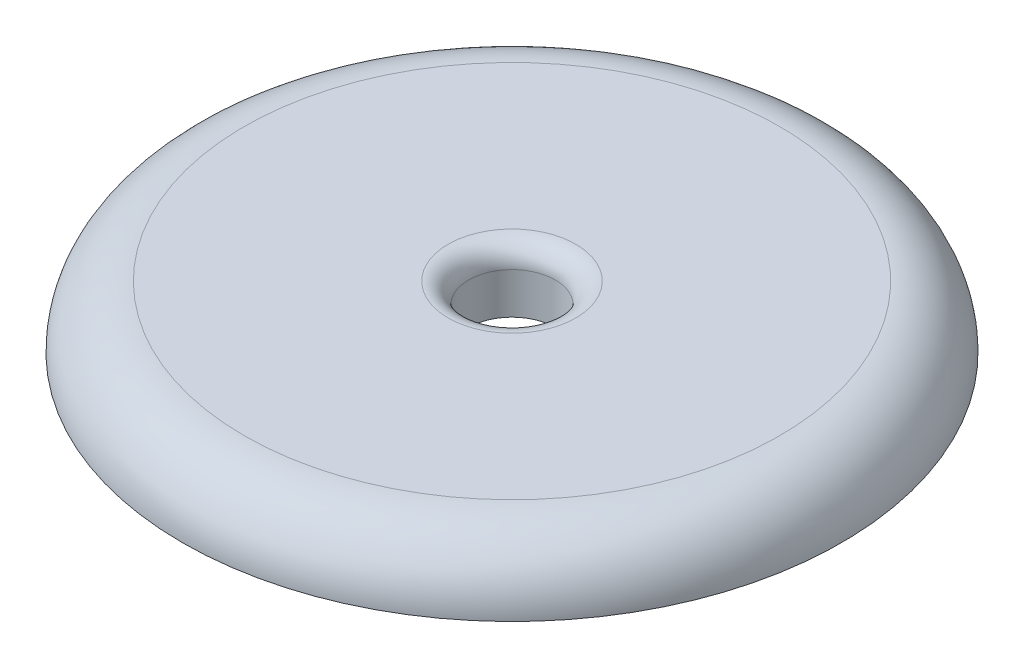
SolidWorks part; units mm, degrees
ref_plane "Спереди" through (0, 0, 0) normal (0, 0, 1) x (1, 0, 0)
ref_plane "Сверху" through (0, 0, 0) normal (0, 1, 0) x (1, 0, 0)
ref_plane "Справа" through (0, 0, 0) normal (1, 0, 0) x (0, 0, -1)
other "Configuration Table"
sketch "Эскиз1" plane through (0, 0, 0) normal (0, 1, 0) x (1, 0, 0)
  line L0 (0, 16.5661) -> (0, -15.4339) construction
  line L1 (-16, 0.5661) -> (16, 0.5661) construction
  circle A0 centre (0, 0.5661) radius 16
  circle A1 centre (0, 0.5661) radius 2.1
  dimension "D1" = 32
  dimension "D2" = 4.2
extrude "Бобышка-Вытянуть1" add sketch "Эскиз1" along normal blind 3
fillet "Скругление1" radius 3 1 edges at (0, 3, 15.4339)
fillet "Скругление2" radius 1 1 edges at (0, 3, 1.5339)
